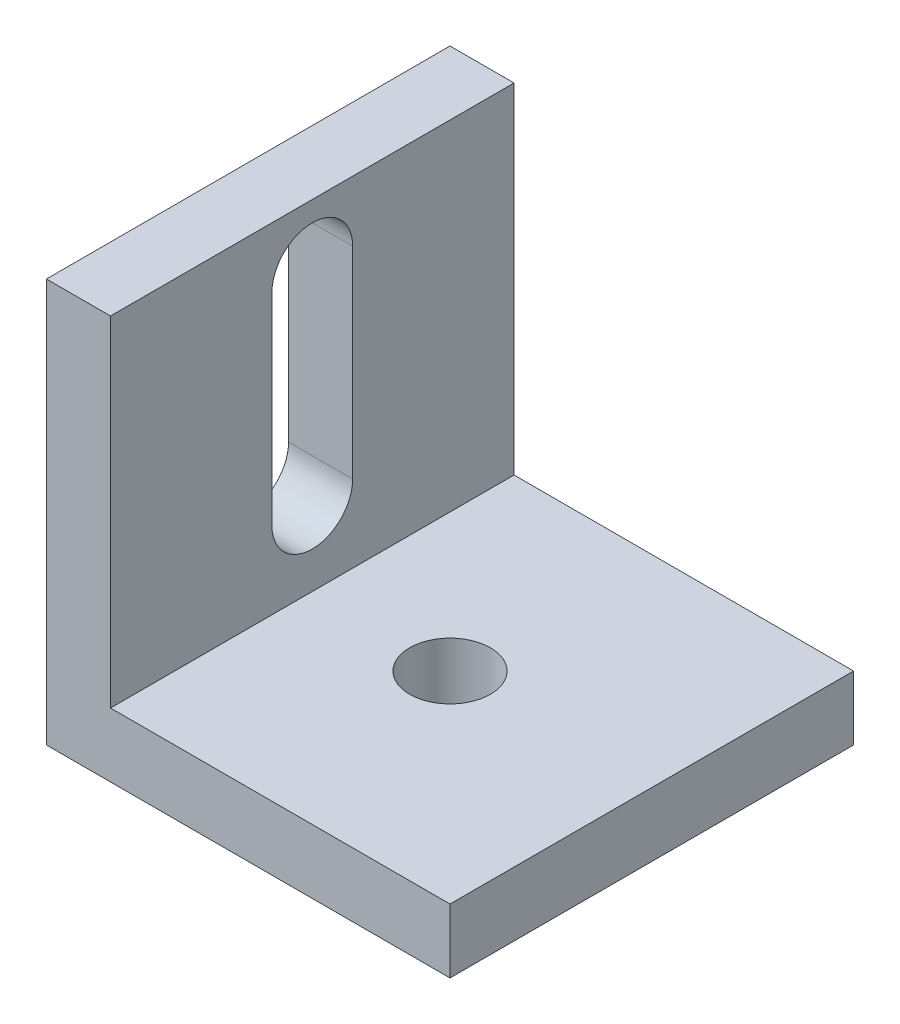
SolidWorks part; units mm, degrees
ref_plane "Front Plane" through (0, 0, 0) normal (0, 0, 1) x (1, 0, 0)
ref_plane "Top Plane" through (0, 0, 0) normal (0, 1, 0) x (1, 0, 0)
ref_plane "Right Plane" through (0, 0, 0) normal (1, 0, 0) x (0, 0, -1)
sketch "Sketch1" plane through (0, 0, 0) normal (0, 0, 1) x (1, 0, 0)
  line L0 (0, 0) -> (0, 16.825)
  line L1 (0, 16.825) -> (-3.175, 16.825)
  line L2 (-3.175, 16.825) -> (-3.175, -3.175)
  line L3 (-3.175, -3.175) -> (16.825, -3.175)
  line L4 (16.825, -3.175) -> (16.825, 0)
  line L5 (16.825, 0) -> (0, 0)
  dimension "D1" = 3.175
  dimension "D2" = 20
extrude "Boss-Extrude1" add sketch "Sketch1" along normal blind 10 and the other way blind 10
sketch "Sketch2" plane through (0, 0, 0) normal (0, 1, 0) x (1, 0, 0)
  line L0 (0, 0) -> (6.825, 0) construction
  line L1 (-3.175, 10) -> (-3.175, -10) construction
  circle A0 centre (6.825, 0) radius 2
  dimension "D1" = 4
  dimension "D2" = 10
extrude "Cut-Extrude1" cut sketch "Sketch2" against normal blind 10
sketch "Sketch3" plane through (0, 0, 0) normal (1, 0, 0) x (0, 0, -1)
  line L0 (0, 0) -> (0, 8.825) construction
  line L1 (10, 0) -> (-10, 0) construction
  line L2 (10, -3.175) -> (-10, -3.175) construction
  line L3 (0, 13.825) -> (0, 3.825) construction
  line L4 (2, 13.825) -> (2, 3.825)
  line L5 (-2, 13.825) -> (-2, 3.825)
  arc A0 (2, 13.825) -> (-2, 13.825) centre (0, 13.825) ccw
  arc A1 (-2, 3.825) -> (2, 3.825) centre (0, 3.825) ccw
  point P8 (0, 8.825)
  point P13 (0, 0)
  dimension "D1" = 12
  dimension "D2" = 10
  dimension "D3" = 4
extrude "Cut-Extrude2" cut sketch "Sketch3" against normal blind 10
